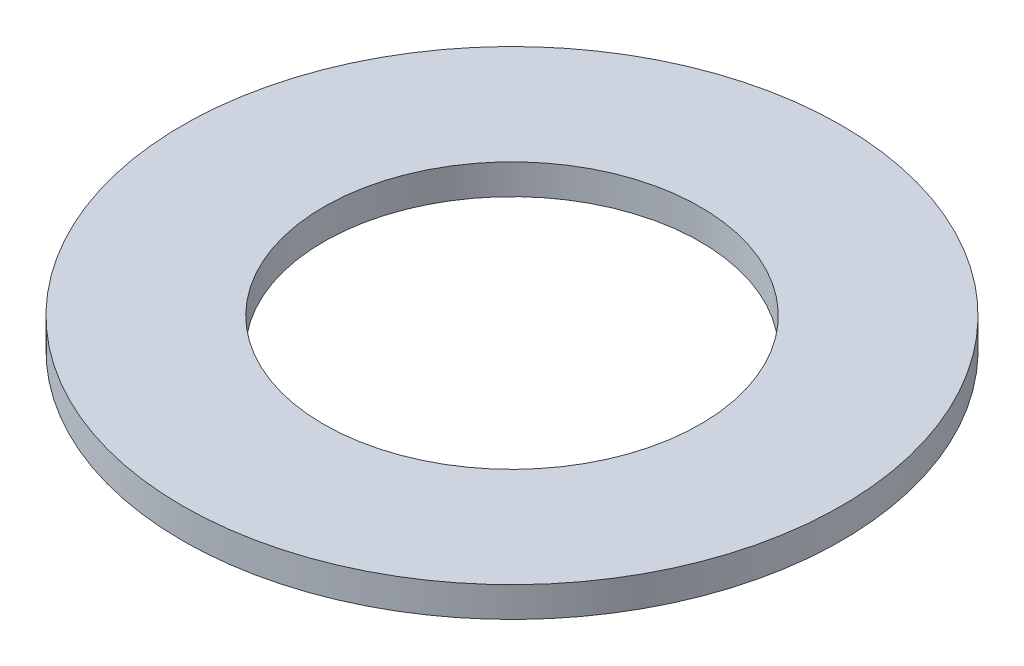
SolidWorks part; units mm, degrees
ref_plane "Front Plane" through (0, 0, 0) normal (0, 0, 1) x (1, 0, 0)
ref_plane "Top Plane" through (0, 0, 0) normal (0, 1, 0) x (1, 0, 0)
ref_plane "Right Plane" through (0, 0, 0) normal (1, 0, 0) x (0, 0, -1)
sketch "Sketch1" plane through (0, 0, 0) normal (0, 1, 0) x (1, 0, 0)
  circle A0 centre (0, 0) radius 87.5
  dimension "FLANGE_OD" = 175
extrude "Boss-Extrude1" add sketch "Sketch1" along normal blind 8
sketch "Sketch2" plane through (0, 0, 0) normal (0, 1, 0) x (1, 0, 0)
  circle A0 centre (0, 0) radius 50
  dimension "BORE_D" = 100
extrude "Cut-Extrude1" cut sketch "Sketch2" along normal through all
sketch "Sketch3" plane through (0, 8, 0) normal (0, 1, 0) x (1, 0, 0)
  circle A0 centre (0, 0) radius 35.9878 construction
  circle A1 centre (-35.9878, 0) radius 4.2777
  dimension "BOLT_D" = 8.5553
  dimension "BOLT_PCD" = 71.9756
extrude "Cut-Extrude2" cut sketch "Sketch3" against normal blind 6.389 rebuild error yes
pattern_circular "CirPattern1" count 3 over 360 rebuild error yes
